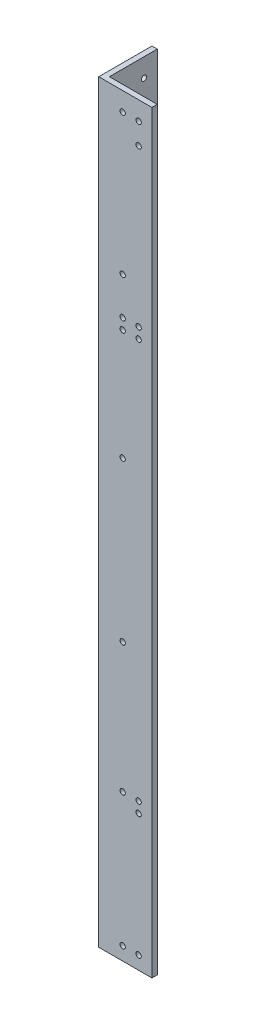
SolidWorks part; units mm, degrees
ref_plane "Front Plane" through (0, 0, 0) normal (0, 0, 1) x (1, 0, 0)
ref_plane "Top Plane" through (0, 0, 0) normal (0, 1, 0) x (1, 0, 0)
ref_plane "Right Plane" through (0, 0, 0) normal (1, 0, 0) x (0, 0, -1)
sketch "Sketch2" plane through (0, 0, 0) normal (0, 1, 0) x (1, 0, 0)
  line L0 (0, 31.75) -> (3.175, 31.75)
  line L1 (3.175, 31.75) -> (3.175, 3.175)
  line L2 (3.175, 3.175) -> (31.75, 3.175)
  line L3 (31.75, 3.175) -> (31.75, 0)
  line L4 (31.75, 0) -> (0, 0)
  line L5 (0, 0) -> (0, 31.75)
  point P9 (1.5875, 31.75)
  point P10 (31.75, 1.5875)
  dimension "D4" = 3.175
  dimension "D1" = 31.75
  dimension "D2" = 31.75
  dimension "D3" = 3.175
extrude "Boss-Extrude1" add sketch "Sketch2" along normal blind 450
sketch "BackSideHoles-Sketch3" plane through (0, 0, 0) normal (0, 0, 1) x (1, 0, 0)
  line L0 (0, 0) -> (31.75, 0) construction
  line L1 (0, 450) -> (0, 0) construction
  circle A1 centre (23.8125, 81.1125) radius 1.5875
  circle A2 centre (14.2875, 87.4625) radius 1.5875
  circle A3 centre (23.8125, 87.4625) radius 1.5875
  circle A4 centre (14.2875, 438.8875) radius 1.5875
  circle A6 centre (23.8125, 438.8875) radius 1.5875
  circle A7 centre (23.8125, 426.1875) radius 1.5875
  circle A10 centre (14.2875, 332.6026) radius 1.5875
  circle A11 centre (23.8125, 332.6026) radius 1.5875
  circle A12 centre (14.2875, 326.2526) radius 1.5875
  circle A13 centre (23.8125, 326.2526) radius 1.5875
  circle A14 centre (14.2875, 165) radius 1.5875
  circle A15 centre (14.2875, 260) radius 1.5875
  circle A16 centre (14.2875, 355) radius 1.5875
  circle A17 centre (14.2875, 7.9375) radius 1.5875
  circle A18 centre (23.8125, 7.9375) radius 1.5875
  dimension "D4" = 3.175
  dimension "D8" = 11.1125
  dimension "D7" = 6.35
  dimension "D10" = 332.6026
  dimension "D11" = 165
  dimension "D12" = 95
  dimension "D13" = 95
  dimension "D6" = 7.9375
  dimension "D5" = 6.35
  dimension "D14" = 81.1125
  dimension "D3" = 9.525
  dimension "D2" = 14.2875
  dimension "D9" = 12.7
sketch "RightSideHoles-Sketch4" plane through (0, 0, 0) normal (-1, 0, 0) x (0, 0, 1)
  line L0 (-31.75, 450) -> (0, 450) construction
  line L1 (0, 450) -> (0, 0) construction
  line L3 (-31.75, 0) -> (0, 0) construction
  circle A0 centre (-23.8125, 81.1125) radius 1.5875
  circle A2 centre (-23.8125, 87.4625) radius 1.5875
  circle A4 centre (-23.8125, 438.8875) radius 1.5875
  circle A5 centre (-14.2875, 426.1875) radius 1.5875
  circle A6 centre (-23.8125, 426.1875) radius 1.5875
  circle A10 centre (-23.8125, 332.6026) radius 1.5875
  circle A11 centre (-14.2875, 332.6026) radius 1.5875
  circle A12 centre (-23.8125, 319.9026) radius 1.5875
  circle A13 centre (-14.2875, 319.9026) radius 1.5875
  circle A14 centre (-23.8125, 7.9375) radius 1.5875
  circle A15 centre (-14.2875, 7.9375) radius 1.5875
  circle A16 centre (-14.2875, 165) radius 1.5875
  circle A17 centre (-14.2875, 260) radius 1.5875
  circle A18 centre (-14.2875, 355) radius 1.5875
  circle A19 centre (-14.2875, 81.1125) radius 1.5875
  dimension "D4" = 3.175
  dimension "D10" = 332.6026
  dimension "D13" = 95
  dimension "D5" = 6.35
  dimension "D2" = 14.2875
  dimension "D9" = 12.7
  dimension "D6" = 11.1125
  dimension "D8" = 7.9375
  dimension "D7" = 12.7
  dimension "D12" = 165
  dimension "D14" = 95
  dimension "D3" = 81.1125
  dimension "D11" = 9.525
extrude "BackSideHoles-Cut-Extrude1" cut sketch "BackSideHoles-Sketch3" against normal blind 3.175
extrude "RightSideHoles-Cut-Extrude2" cut sketch "RightSideHoles-Sketch4" against normal blind 3.175
equation "\"RailThickness\"= .125in'Spec"
equation "\"VSWidth\"= 1.25in'Spec"
equation "\"VSHeight\"= 1.25in'Spec"
equation "\"VSLength\"= 450mm"
equation "\"HoleOffsetFromEdge\"= \"RailThickness\" * 2.5"
equation "\"HoleOffsetFromSide\"= \"RailThickness\" * 3.5"
equation "\"LegHeight\"= 70mm'Space needed for PSU/Stepper/Electronics"
equation "\"VSBottomSideRailHoleY1FromBottomOfLowerRail\"= \"V1 BottomOfLowerRail\" + \"HoleOffsetFromSide\"'Equals 70.1125"
equation "\"VSSideRailHoleX1FromSide\"= \"HoleOffsetFromSide\" + \"RailThickness\""
equation "\"FasteningHoleDiameter\"= .125in"
equation "\"VSBottomSideRailHoleY2FromY1\"= \"LowerRailHeight\" - \"HoleOffsetFromSide\" - \"HoleOffsetFromEdge\"'Equals 6.35"
equation "\"VSTopSideRailHoleY1FromEdge\"= \"HoleOffsetFromEdge\" + \"RailThickness\""
equation "\"D4@BackSideHoles-Sketch3\" = \"FasteningHoleDiameter\""
equation "\"D1@Boss-Extrude1\"=\"VSLength\""
equation "\"D4@RightSideHoles-Sketch4\"=\"FasteningHoleDiameter\""
equation "\"D8@BackSideHoles-Sketch3\" = \"VSTopSideRailHoleY1FromEdge\""
equation "\"D6@RightSideHoles-Sketch4\"=\"VSTopSideRailHoleY1FromEdge\""
equation "\"VSMidSideRailHoleY1FromV8TopOfMidSideRail\"= \"V8 ToTopOfMidSideRail\" - \"HoleOffsetFromEdge\"'Equals 308.2875"
equation "\"LowerRailHeight\"= 1.00in"
equation "\"D2@Sketch2\"=\"VSWidth\""
equation "\"D1@Sketch2\"=\"VSHeight\""
equation "\"MidBackRailHeight\"= 1.00in"
equation "\"VSMidBackRailHoleY1FromV7TopOfMidBackRail\"= \"V7 ToTopOfMidBackRail\" - \"HoleOffsetFromSide\"'Equals 308.2875"
equation "\"TopRailHeight\"= 1.25in"
equation "\"MidSideRailHeight\"= 1.25in"
equation "\"D8@RightSideHoles-Sketch4\"=\"HoleOffsetFromEdge\""
equation "\"VSMidBackRailHoleY2FromY1\"= \"MidBackRailHeight\" - \"HoleOffsetFromSide\" - \"HoleOffsetFromEdge\"'Equals 6.35"
equation "\"VSMidSideRailHoleY2FromY1\"= \"MidSideRailHeight\" - \"HoleOffsetFromSide\" - \"HoleOffsetFromEdge\"'Equals 12.7"
equation "\"D7@BackSideHoles-Sketch3\"=\"VSMidBackRailHoleY2FromY1\""
equation "\"D9@RightSideHoles-Sketch4\"=\"VSMidSideRailHoleY2FromY1\""
equation "\"VSTopSideRailHoleY2FromY1\"= \"TopRailHeight\" - \"VSTopSideRailHoleY1FromEdge\" - \"HoleOffsetFromEdge\"'Equals 12.7"
equation "\"VSSideRailHoleX2FromX1\"= \"VSWidth\" - \"VSSideRailHoleX1FromSide\" - \"HoleOffsetFromEdge\""
equation "\"D7@RightSideHoles-Sketch4\"=\"VSTopSideRailHoleY2FromY1\""
equation "\"V1 BottomOfLowerRail\"= \"LegHeight\""
equation "\"StepperShaftLength\"= 24mm'Pulley will be attached to the end"
equation "\"ZAxisLeadScrewLength\"= 200mm"
equation "\"HotEndToTopOfXAxisGB\"= 63.315144mm'Measured from the100.Should be 63.315144"
equation "\"TopOfGBToBottomOfLinearRail\"= \"LinearGBWidth\" / 2 + \"LinearRailWidth\" / 2"
equation "\"LinearGBWidth\"= 27mm'Spec"
equation "\"V5 ToBottomOfXAxisLinearRail\"= \"V4 ToTopOfBuildPlate/HotEndTip\" + \"HotEndToTopOfXAxisGB\" - \"TopOfGBToBottomOfLinearRail\""
equation "\"LinearRailWidth\"= 12mm'Spec"
equation "\"V6 ToBottomOfGantryPulley\"= \"V5 ToBottomOfXAxisLinearRail\" - \"DistanceFromGABTopToLowerPulley\""
equation "\"GABUpperHeight\"= 6mm"
equation "\"GABMidWallHeight\"= 28mm'Must equal 28 or changes alignment"
equation "\"20TGT2PulleyWidth\"= 8.7mm'The STL of the Pulley in the diagram is a bit larger"
equation "\"GABMidShortRiserHeight\"= \"GABMidWallHeight\" / 2 - \"20TGT2PulleyWidth\"'Equals 5.3"
equation "\"GABRiserBossOffset\"= 0.8mm'Aligns Pulleys"
equation "\"DistanceFromGABTopToLowerPulley\"= \"GABUpperHeight\" + \"GABMidWallHeight\" - \"GABMidShortRiserHeight\" + \"GABRiserBossOffset\" / 2"
equation "\"V7 ToTopOfMidBackRail\"= \"V6 ToBottomOfGantryPulley\" + \"StepperShaftLength\""
equation "\"D10@BackSideHoles-Sketch3\" = \"VSMidBackRailHoleY1FromV7TopOfMidBackRail\""
equation "\"D10@RightSideHoles-Sketch4\"=\"VSMidSideRailHoleY1FromV8TopOfMidSideRail\""
equation "\"BedToBuildPlateStandoffLength\"= 15mm"
equation "\"BuildPlateHeight\"= 8mm'Spec"
equation "\"V4 ToTopOfBuildPlate/HotEndTip\"= \"V2 ToBedAtTopOfZAxis\" + \"BedToBuildPlateStandoffLength\" + \"BuildPlateHeight\""
equation "\"V2 ToBedAtTopOfZAxis\"= \"V1 BottomOfLowerRail\" + \"StepperShaftLength\" + \"ZAxisLeadScrewLength\" - \"LM8UUHeight\" / 2"
equation "\"LM8UUHeight\"= 24mm'Spec"
equation "\"V8 ToTopOfMidSideRail\"= \"V7 ToTopOfMidBackRail\" - \"RailThickness\""
equation "\"VSEnclosureOffsets\"= ( \"VSLength\" - \"LegHeight\" ) / 4"
equation "\"D11@BackSideHoles-Sketch3\"=\"LegHeight\" + \"VSEnclosureOffsets\""
equation "\"D12@BackSideHoles-Sketch3\"=\"VSEnclosureOffsets\""
equation "\"D13@BackSideHoles-Sketch3\"=\"VSEnclosureOffsets\""
equation "\"D12@RightSideHoles-Sketch4\"=\"LegHeight\" + \"VSEnclosureOffsets\""
equation "\"D13@RightSideHoles-Sketch4\"=\"VSEnclosureOffsets\""
equation "\"D14@RightSideHoles-Sketch4\"=\"VSEnclosureOffsets\""
equation "\"D6@BackSideHoles-Sketch3\"=\"HoleOffsetFromEdge\""
equation "\"D5@BackSideHoles-Sketch3\"=\"VSBottomSideRailHoleY2FromY1\""
equation "\"D14@BackSideHoles-Sketch3\"=\"VSBottomSideRailHoleY1FromBottomOfLowerRail\""
equation "\"D2@BackSideHoles-Sketch3\"=\"VSSideRailHoleX1FromSide\""
equation "\"D9@BackSideHoles-Sketch3\"=\"VSTopSideRailHoleY2FromY1\""
equation "\"D3@RightSideHoles-Sketch4\"=\"VSBottomSideRailHoleY1FromBottomOfLowerRail\""
equation "\"D5@RightSideHoles-Sketch4\"=\"VSBottomSideRailHoleY2FromY1\""
equation "\"D2@RightSideHoles-Sketch4\"=\"VSSideRailHoleX1FromSide\""
equation "\"D11@RightSideHoles-Sketch4\"=\"VSSideRailHoleX2FromX1\""
